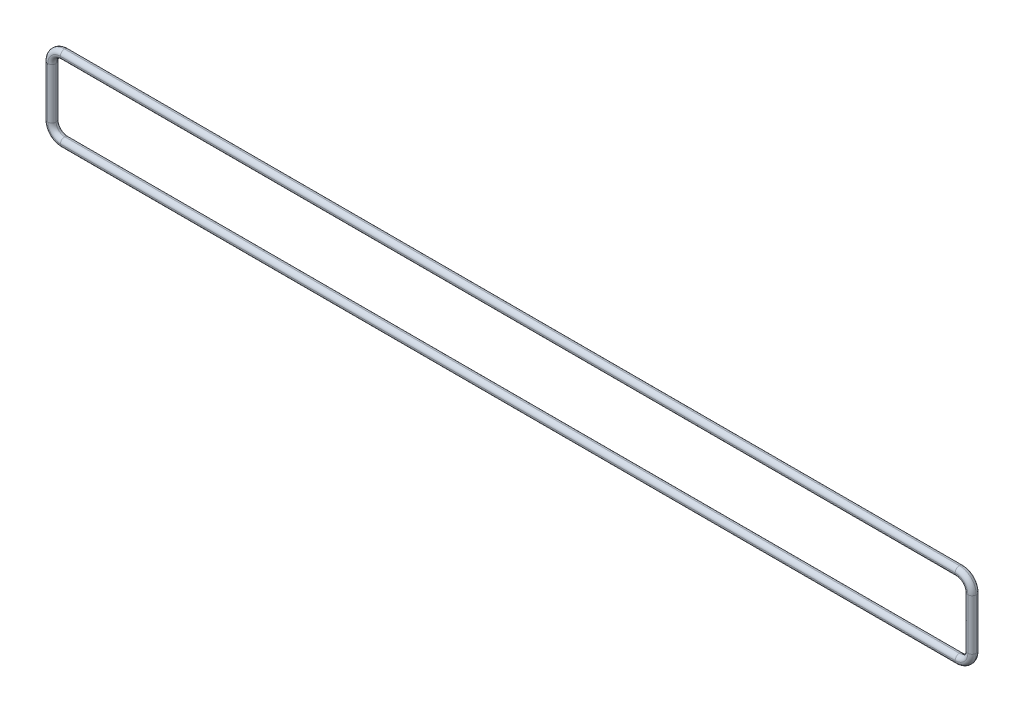
SolidWorks part; units mm, degrees
ref_plane "Front Plane" through (0, 0, 0) normal (0, 0, 1) x (1, 0, 0)
ref_plane "Top Plane" through (0, 0, 0) normal (0, 1, 0) x (1, 0, 0)
ref_plane "Right Plane" through (0, 0, 0) normal (1, 0, 0) x (0, 0, -1)
sketch "Sketch2" plane through (0, 0, 0) normal (0, 0, 1) x (1, 0, 0)
  line L0 (0, 0) -> (0, 38.1)
  line L1 (6.35, 38.1) -> (6.35, 0)
  line L2 (0, 19.05) -> (6.35, 19.05) construction
  line L3 (12.7, 50.8) -> (685.8, 50.8)
  line L4 (12.7, 44.45) -> (685.8, 44.45)
  line L5 (12.7, -6.35) -> (685.8, -6.35)
  line L6 (12.7, -12.7) -> (685.8, -12.7)
  line L7 (349.25, -12.7) -> (349.25, 50.8) construction
  line L8 (698.5, 0) -> (698.5, 38.1)
  line L9 (692.15, 38.1) -> (692.15, 0)
  arc A0 (0, 38.1) -> (12.7, 50.8) centre (12.7, 38.1) cw
  arc A1 (0, 0) -> (12.7, -12.7) centre (12.7, 0) ccw
  arc A2 (6.35, 38.1) -> (12.7, 44.45) centre (12.7, 38.1) cw
  arc A3 (6.35, 0) -> (12.7, -6.35) centre (12.7, 0) ccw
  arc A4 (698.5, 0) -> (685.8, -12.7) centre (685.8, 0) cw
  arc A5 (692.15, 0) -> (685.8, -6.35) centre (685.8, 0) cw
  arc A6 (698.5, 38.1) -> (685.8, 50.8) centre (685.8, 38.1) ccw
  arc A7 (692.15, 38.1) -> (685.8, 44.45) centre (685.8, 38.1) ccw
  point P12 (349.25, -6.35)
  point P28 (349.25, 44.45)
  dimension "D1" = 38.1
  dimension "D2" = 6.35
  dimension "D3" = 38.1
  dimension "D4" = 6.35
  dimension "D5" = 342.9
extrude "Boss-Extrude1" add sketch "Sketch2" along normal blind 6.35
fillet "Fillet3" radius 3.175 32 edges at (0, 19.05, 6.35) (3.7197, 47.0803, 6.35) (349.25, 50.8, 6.35) (694.7803, 47.0803, 6.35) (698.5, 19.05, 6.35) (694.7803, -8.9803, 6.35) (349.25, -12.7, 6.35) (3.7197, -8.9803, 6.35) (0, 19.05, 0) (3.7197, 47.0803, 0) (349.25, 50.8, 0) (694.7803, 47.0803, 0) (698.5, 19.05, 0) (694.7803, -8.9803, 0) (349.25, -12.7, 0) (3.7197, -8.9803, 0) (349.25, 44.45, 6.35) (690.2901, 42.5901, 6.35) (692.15, 19.05, 6.35) (690.2901, -4.4901, 6.35) (349.25, -6.35, 6.35) (8.2099, -4.4901, 6.35) (6.35, 19.05, 6.35) (8.2099, 42.5901, 6.35) (349.25, 44.45, 0) (690.2901, 42.5901, 0) (692.15, 19.05, 0) (690.2901, -4.4901, 0) (349.25, -6.35, 0) (8.2099, -4.4901, 0) (6.35, 19.05, 0) (8.2099, 42.5901, 0)
